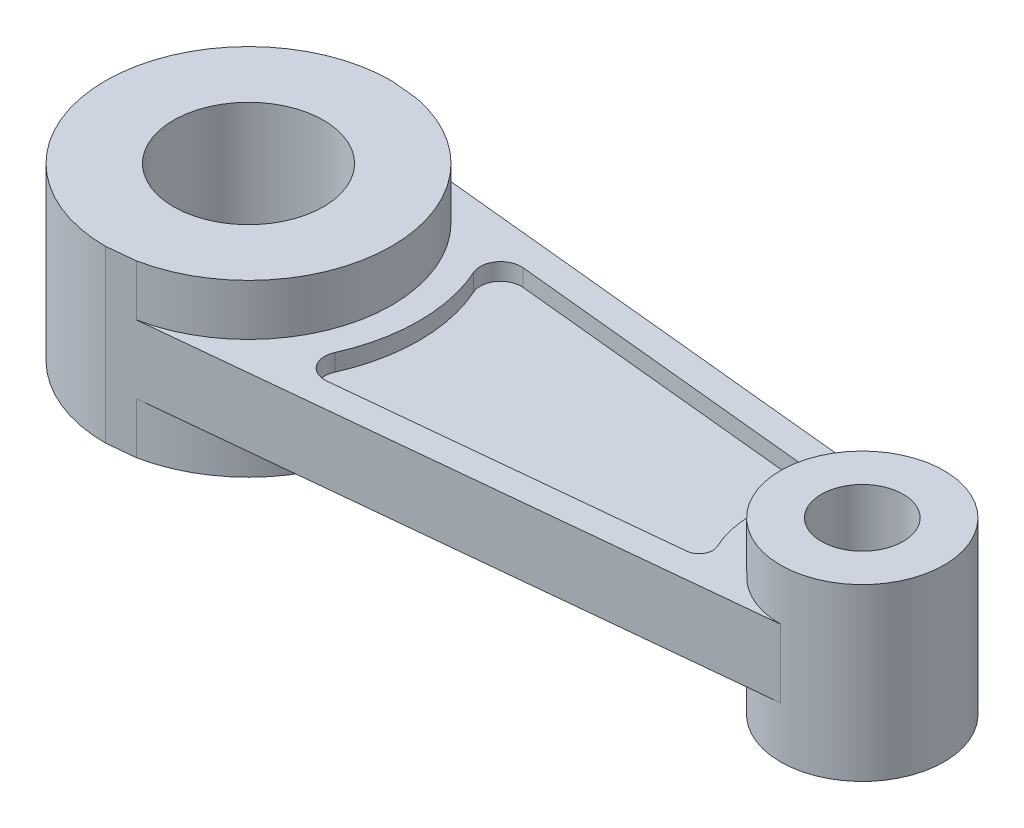
SolidWorks part; units mm, degrees
ref_plane "Front Plane" through (0, 0, 0) normal (0, 0, 1) x (1, 0, 0)
ref_plane "Top Plane" through (0, 0, 0) normal (0, 1, 0) x (1, 0, 0)
ref_plane "Right Plane" through (0, 0, 0) normal (1, 0, 0) x (0, 0, -1)
sketch "Sketch2" plane through (0, 0, 0) normal (0, 1, 0) x (1, 0, 0)
  line L0 (-33.4664, -21) -> (56.5336, -12)
  line L1 (-33.4664, 21) -> (56.5336, 12)
  line L2 (-7.5972, 14.3931) -> (40.4166, 9.5918)
  line L3 (-7.5972, -14.3931) -> (40.4166, -9.5918)
  circle A0 centre (-33.4664, 0) radius 11
  circle A1 centre (-33.4664, 0) radius 21
  circle A2 centre (56.5336, 0) radius 6
  circle A3 centre (56.5336, 0) radius 12
  arc A4 (-7.5972, -14.3931) -> (-10.6354, -10.1857) centre (-7.8957, -11.408) cw
  arc A5 (-7.5972, 14.3931) -> (-10.6354, 10.1857) centre (-7.8957, 11.408) ccw
  arc A6 (-10.6354, -10.1857) -> (-10.6354, 10.1857) centre (-33.4664, 0) ccw
  arc A7 (40.4166, -9.5918) -> (42.0305, -6.7571) centre (40.2176, -7.6017) ccw
  arc A8 (42.0305, 6.7571) -> (42.0305, -6.7571) centre (56.5336, 0) ccw
  arc A9 (40.4166, 9.5918) -> (42.0305, 6.7571) centre (40.2176, 7.6017) cw
  point P25 (0, 0)
  dimension "D1" = 22
  dimension "D2" = 42
  dimension "D3" = 12
  dimension "D4" = 24
  dimension "D5" = 90
  dimension "D6" = 56.5336
extrude "Boss-Extrude1" add sketch "Sketch2" along normal mid plane 25 contours L0 A1 L1 A0 | A3 A2 region at (-53.8724, 0, 0) region at (44.8731, 0, 0)
extrude "Boss-Extrude2" add sketch "Sketch2<3>" along normal mid plane 10 contours A3 L1 A1 L0 region at (-16.4764, 0, 13.9009)
sketch "Sketch2<3>" plane through (0, 0, 0) normal (0, 1, 0) x (1, 0, 0) same geometry as "Sketch2"
extrude "Boss-Extrude3" add sketch "Sketch2<4>" along normal mid plane 5 contours A6 A5 L2 A9 A8 A7 L3 A4
sketch "Sketch2<4>" plane through (0, 0, 0) normal (0, 1, 0) x (1, 0, 0) same geometry as "Sketch2"
